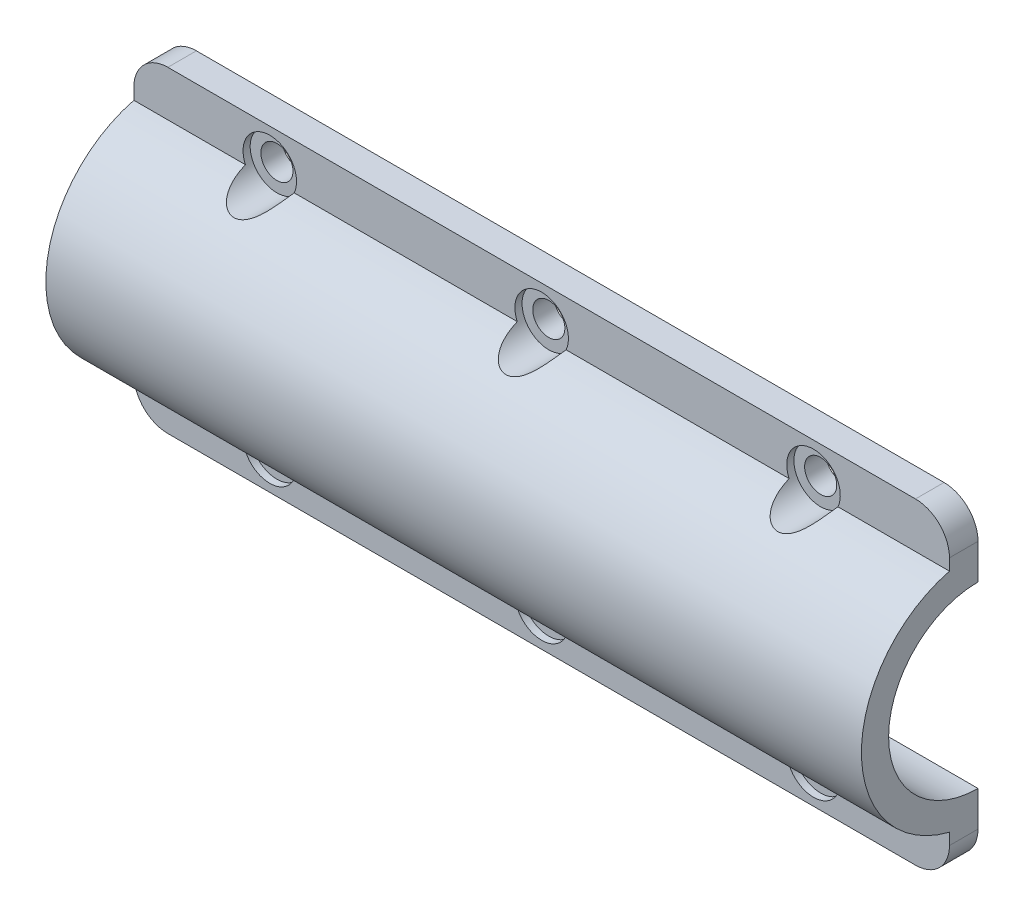
SolidWorks part; units mm, degrees
material "Custom Plastic"
ref_plane "X-Y Datum" through (0, 0, 0) normal (0, 0, 1) x (1, 0, 0)
ref_plane "X-Z Datum" through (0, 0, 0) normal (0, 1, 0) x (1, 0, 0)
ref_plane "Y-Z Datum" through (0, 0, 0) normal (1, 0, 0) x (0, 0, -1)
sketch "Sketch1" plane through (0, 0, 0) normal (1, 0, 0) x (0, 0, -1)
  line L0 (0, 22.225) -> (0, 17.4625) construction
  line L1 (-4, 22.225) -> (-4, 15.8396)
  line L2 (0, -22.225) -> (-4, -22.225)
  line L3 (-4, 11.8711) -> (-4, 11.3422)
  line L4 (-4, -15.8396) -> (-4, -22.225)
  line L7 (23.8125, 12.065) -> (17.8125, 12.065)
  line L8 (23.8125, -17.4625) -> (23.8125, 12.065)
  line L9 (17.8125, 17.4625) -> (0, 17.4625)
  line L10 (0, -12.5269) -> (0, -17.4625)
  line L11 (0, 17.4625) -> (0, 12.5269)
  line L12 (17.8125, 17.4625) -> (0, 17.4625)
  line L13 (17.8125, 12.065) -> (17.8125, 17.4625)
  line L14 (23.8125, 12.065) -> (17.8125, 12.065)
  line L15 (23.8125, -17.4625) -> (23.8125, 12.065)
  line L17 (0, -12.5269) -> (0, -17.4625)
  line L18 (0, 17.4625) -> (0, 12.5269)
  line L20 (17.8125, 12.065) -> (17.8125, 17.4625)
  line L27 (17.8125, 22.225) -> (0, 22.225) construction
  line L28 (17.8125, 22.225) -> (-4, 22.225)
  line L29 (0, 22.225) -> (0, 17.4625)
  line L31 (0, -22.225) -> (23.8125, -22.225) construction
  line L32 (0, -22.225) -> (23.8125, -22.225)
  line L33 (0, -17.4625) -> (23.8125, -17.4625)
  line L34 (0, -17.4625) -> (23.8125, -17.4625)
  line L35 (0, -17.4625) -> (0, -22.225) construction
  line L36 (0, -17.4625) -> (0, -22.225)
  circle A0 centre (0, 0) radius 12.5269
  arc A1 (0, -12.5269) -> (0, 12.5269) centre (0, 0) ccw
  arc A2 (0, -12.5269) -> (0, 12.5269) centre (0, 0) ccw
  circle A3 centre (0, 0) radius 12.0269
  circle A4 centre (0, 0) radius 12.0269
  circle A5 centre (0, 0) radius 16.3369
  dimension "D5" = 4
  dimension "D1" = 0
  dimension "D2" = 0
  dimension "D3" = 0.5
  dimension "D4" = 3.81
extrude "Boss-Extrude1" add sketch "Sketch1" along normal blind 114.3 contours A5 L18 L1 | L18 A5 L17 A0 | A5 L4 L17 region at (0, 19.1968, 2.0273) region at (0, 15.8496, 1.9703) region at (0, -19.1968, 2.0273)
sketch "Sketch2" plane through (0, 0, 4) normal (0, 0, 1) x (1, 0, 0)
  circle A0 centre (19.05, -17.3759) radius 3.75
  circle A1 centre (57.15, -17.3759) radius 3.75
  circle A2 centre (95.25, -17.3759) radius 3.75
  point P0 (19.05, -17.3759)
  point P1 (57.15, -17.3759)
  point P3 (95.25, -17.3759)
  dimension "D1" = 7.5
extrude "Cut-Extrude1" cut sketch "Sketch2" against normal blind 1 and the other way blind 6.35
hole_wizard "M4 Clearance Hole1" positions "Sketch7" profile "Sketch6" hole size "M4" standard "ANSI Metric" end condition through all
sketch "Sketch7" plane through (0, 0, 4) normal (0, 0, 1) x (1, 0, 0)
  point P0 (19.05, -17.3759)
  point P3 (57.15, -17.3759)
  point P6 (95.25, -17.3759)
sketch "Sketch6" plane through (19.05, -17.3759, 4) normal (1, 0, 0) x (0, -1, 0)
  line L0 (0, 0) -> (0, 4)
  line L1 (0, 4) -> (2.25, 4)
  line L2 (2.25, 4) -> (2.25, 0)
  line L5 (2.25, 0) -> (0, 0)
  line L11 (0, -6.35) -> (0, 107.95) construction
  dimension "Thru Hole Dia." = 4.5
  dimension "Thru Hole Depth" = 4
mirror "Mirror1" about plane through (0, 0, 0) normal (0, 1, 0) of "M4 Clearance Hole1", "Cut-Extrude1"
fillet "Fillet1" radius 4.7625 4 edges at (114.3, 22.225, 2) (114.3, -22.225, 2) (0, 22.225, 2) (0, -22.225, 2)
